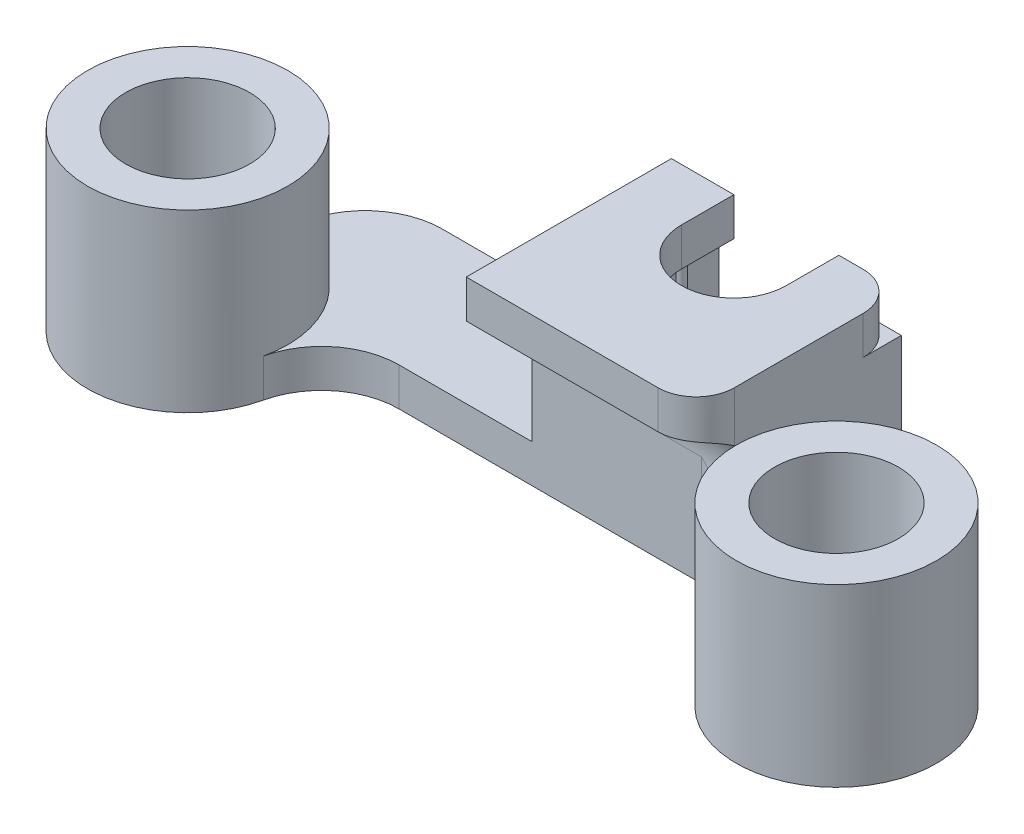
SolidWorks part; units mm, degrees
ref_plane "Front Plane" through (0, 0, 0) normal (0, 0, 1) x (1, 0, 0)
ref_plane "Top Plane" through (0, 0, 0) normal (0, 1, 0) x (1, 0, 0)
ref_plane "Right Plane" through (0, 0, 0) normal (1, 0, 0) x (0, 0, -1)
sketch "Sketch1" plane through (0, 0, 0) normal (0, 1, 0) x (1, 0, 0)
  line L0 (-22.0834, 0) -> (18.4225, 0) construction
  line L1 (0, 28.6375) -> (0, -13.7578) construction
  line L2 (-30.3285, 5) -> (25.9686, 5) construction
  circle A0 centre (-17, 0) radius 3.25
  circle A1 centre (17, 0) radius 3.25
  circle A2 centre (-17, 0) radius 5.25
  circle A3 centre (17, 0) radius 5.25
  dimension "D1" = 6.5
  dimension "D3" = 2
  dimension "D2" = 34
  dimension "D4" = 5
extrude "Boss-Extrude1" add sketch "Sketch1" along normal blind 9.2
sketch "Sketch2" plane through (0, 0, 0) normal (0, 1, 0) x (1, 0, 0)
  line L0 (-17, 0) -> (17, 0) construction
  line L2 (-17, 9.3) -> (17, 9.3)
  line L3 (-17, 9.3) -> (-17, 2)
  line L4 (-17, 2) -> (17, 2)
  line L5 (17, 9.3) -> (17, 2)
  line L6 (-17, 9.3) -> (17, 2) construction
  line L7 (-17, 2) -> (17, 9.3) construction
  circle A1 centre (17, 0) radius 3.25 construction
  circle A3 centre (-17, 0) radius 3.25 construction
  circle A4 centre (17, 0) radius 3.25
  circle A5 centre (-17, 0) radius 3.25
  point P4 (0, 5.65)
  dimension "D1" = 4
  dimension "D2" = 7.3
extrude "Boss-Extrude2" add sketch "Sketch2" along normal blind 2 contours A5 L4 A4 L5 L2 L3
sketch "Sketch3" plane through (0, 2, 0) normal (0, 1, 0) x (1, 0, 0)
  line L0 (1.8, 8.1657) -> (1.8, 0.5657) construction
  line L1 (1.8, 8.1657) -> (1.8, 0.5657)
  line L2 (8.35, 8.1657) -> (8.35, 0.5657) construction
  line L3 (8.35, 8.1657) -> (8.35, 0.5657)
  line L4 (-17, 9.3) -> (17, 9.3) construction
  line L5 (1.55, 9.3) -> (8.6, 9.3)
  line L6 (1.55, 9.3) -> (1.55, 2)
  line L7 (1.55, 2) -> (8.6, 2)
  line L8 (8.6, 9.3) -> (8.6, 2)
  line L9 (-12.1459, 2) -> (12.1459, 2) construction
  line L10 (1.55, 5.65) -> (1.8, 5.65) construction
  line L11 (1.55, 9.3) -> (-0.95, 9.3)
  line L12 (1.55, 9.3) -> (1.55, 2)
  line L13 (1.55, 2) -> (-0.95, 2)
  line L14 (-0.95, 9.3) -> (-0.95, 2)
  line L15 (8.6, 9.3) -> (11.1, 9.3)
  line L16 (8.6, 9.3) -> (8.6, 2)
  line L17 (8.6, 2) -> (11.1, 2)
  line L18 (11.1, 9.3) -> (11.1, 2)
  line L19 (8.35, 4.3657) -> (8.6, 4.3657) construction
  line M1 (-12.1459, 2) -> (12.1459, 2)
  line M4 (17, 9.3) -> (-17, 9.3)
  dimension "D1" = 0.25
  dimension "D3" = 2.5
extrude "Boss-Extrude3" add sketch "Sketch3" along normal up to surface (7.2 mm away) contours L14 L6 M4 M1 | L18 L8 M4 M1 up to face at (17, 9.2, -5.25)
ref_plane "Plane1" through (10.3358, 9.2, 2) normal (1, 0, 0) x (0, 0, -1)
sketch "Sketch5" plane through (0, 9.2, 0) normal (0, 1, 0) x (1, 0, 0)
  line L1 (11.1, 2) -> (11.1, 9.3) construction
  line L3 (-0.95, 9.3) -> (9.1, 9.3)
  line L5 (-0.95, 9.3) -> (-0.95, -1.45)
  line L6 (-0.95, -1.45) -> (9.1, -1.45)
  line L8 (11.1, 7.3) -> (11.1, 0.55)
  line L9 (1.55, 9.3) -> (8.6, 9.3) construction
  line L10 (1.55, 9.3) -> (8.6, 9.3)
  line L11 (1.55, 9.3) -> (1.55, 2)
  line L12 (1.55, 2) -> (8.6, 2)
  line L13 (8.6, 9.3) -> (8.6, 2)
  line L14 (5.075, 2) -> (5.075, 9.3) construction
  line L15 (2.325, 6.55) -> (2.325, 9.3)
  line L16 (7.825, 6.55) -> (7.825, 9.3)
  arc A1 (9.1, -1.45) -> (11.1, 0.55) centre (9.1, 0.55) ccw
  arc A3 (9.1, 9.3) -> (11.1, 7.3) centre (9.1, 7.3) cw
  circle A4 centre (5.075, 6.55) radius 2.75
  point P8 (11.1, -1.45)
  point P11 (11.1, 9.3)
  line M1 (11.1, 2) -> (11.1, 9.3)
  line M2 (11.1, 9.3) -> (8.6, 9.3)
  line M3 (8.6, 9.3) -> (8.6, 2)
  line M4 (8.6, 2) -> (11.1, 2)
  dimension "D2" = 2
  dimension "D3" = 5.5
  dimension "D1" = 10.75
extrude "Boss-Extrude4" add sketch "Sketch5" along normal blind 2 contours L6 A1 L8 L12 L11 L3 L5 M4 | A3 M2 M3 M4 M1 | A4 L15 L3 L11 L12 L16 M3
sketch "Sketch6" plane through (0, 2, 0) normal (0, 1, 0) x (1, 0, 0)
  line L0 (1.55, 9.3) -> (1.55, 2) construction
  line L3 (1.55, 9.3) -> (8.6, 9.3) construction
  line L4 (1.55, 2) -> (8.6, 2) construction
  line L5 (8.6, 9.3) -> (8.6, 2) construction
  circle A0 centre (1.55, 7.3) radius 0.25
  circle A1 centre (1.55, 4) radius 0.25
  circle A2 centre (8.6, 7.3) radius 0.25
  circle A3 centre (8.6, 4) radius 0.25
  dimension "D1" = 0.5
  dimension "D2" = 2
  dimension "D3" = 2
extrude "Boss-Extrude5" add sketch "Sketch6" along normal up to surface (7.2 mm away) up to face at (17, 9.2, -5.25)
sketch "Sketch7" plane through (0, 2, 0) normal (0, 1, 0) x (1, 0, 0)
  line L0 (8.6, 3.75) -> (8.6, 2) construction
  line L1 (1.55, 2) -> (8.6, 2)
  line L2 (1.55, 2) -> (1.55, 3)
  line L3 (1.55, 3) -> (8.6, 3)
  line L4 (8.6, 2) -> (8.6, 3)
  dimension "D1" = 1
extrude "Boss-Extrude6" add sketch "Sketch7" along normal up to next
fillet "Fillet3" radius 3.45 1 edges at (5.075, 9.2, -2)
fillet "Fillet4" radius 4.05 4 edges at (12.1459, 1, -2) (-12.1459, 1, -2) (17, 1, -9.3) (-17, 1, -9.3)
